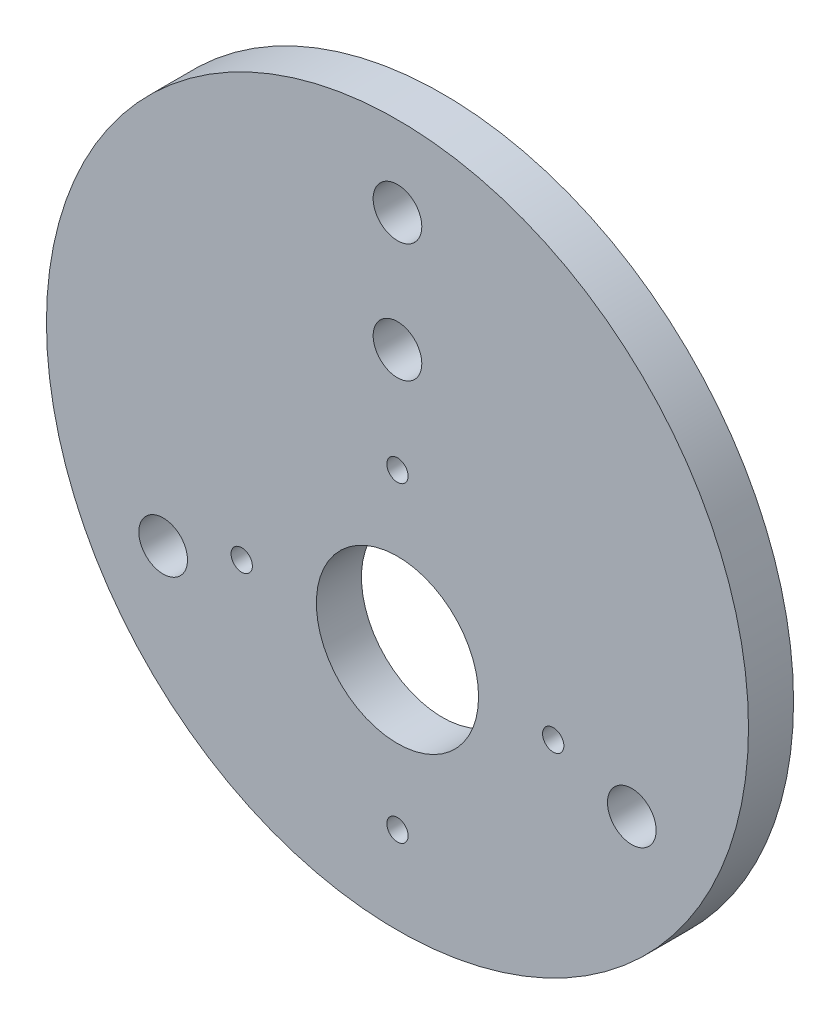
SolidWorks part; units mm, degrees
ref_plane "Front Plane" through (0, 0, 0) normal (0, 0, 1) x (1, 0, 0)
ref_plane "Top Plane" through (0, 0, 0) normal (0, 1, 0) x (1, 0, 0)
ref_plane "Right Plane" through (0, 0, 0) normal (1, 0, 0) x (0, 0, -1)
sketch "Sketch1" plane through (0, 0, 0) normal (0, 0, 1) x (1, 0, 0)
  circle A0 centre (0, 0) radius 49.4665
  dimension "D1" = 98.933
extrude "Boss-Extrude1" add sketch "Sketch1" along normal blind 6.35
sketch "Sketch2" plane through (0, 0, 6.35) normal (0, 0, 1) x (1, 0, 0)
  line L0 (0, -37.1877) -> (0, 6.7077) construction
  line L1 (-21.9477, -15.24) -> (0, 6.7077)
  line L2 (-21.9477, -15.24) -> (0, -37.1877)
  line L3 (0, -37.1877) -> (21.9477, -15.24)
  line L4 (0, 6.7077) -> (21.9477, -15.24)
  line L5 (0, -15.24) -> (12.0918, -15.24) construction
  point P4 (0, -15.24)
  dimension "D1" = 31.0388
  dimension "D2" = 31.0388
  dimension "D3" = 15.24
  dimension "D4" = 90
hole_wizard "M3 Screw Hole - Ø3.0mm Dowel Hole" positions "Sketch3" profile "Sketch4" hole size "Ø3.0" standard "ANSI Metric" end condition through all
sketch "Sketch3" plane through (0, 0, 6.35) normal (0, 0, 1) x (1, 0, 0)
  point P0 (0, 6.7077)
  point P3 (-21.9477, -15.24)
  point P6 (0, -37.1877)
  point P9 (21.9477, -15.24)
sketch "Sketch4" plane through (0, 6.7077, 6.35) normal (1, 0, 0) x (0, -1, 0)
  line L0 (0, 0) -> (0, 6.35)
  line L1 (0, 6.35) -> (1.5, 6.35)
  line L2 (1.5, 6.35) -> (1.5, 0)
  line L5 (1.5, 0) -> (0, 0)
  line L11 (0, -6.35) -> (0, 107.95) construction
  dimension "Thru Hole Dia." = 3
  dimension "Thru Hole Depth" = 6.35
sketch "Sketch5" plane through (0, 0, 6.35) normal (0, 0, 1) x (1, 0, 0)
  line L0 (0, -37.1877) -> (0, 6.7077) construction
  line L1 (-29.9941, -15.24) -> (0, 14.7541)
  line L2 (-29.9941, -15.24) -> (0, -45.2341)
  line L3 (0, -45.2341) -> (29.9941, -15.24)
  line L4 (0, 14.7541) -> (29.9941, -15.24)
  line L5 (-29.9941, -15.24) -> (29.9941, -15.24) construction
  line L6 (0, -45.2341) -> (0, 14.7541) construction
  line L7 (-19.3974, 4.1574) -> (0, -15.24) construction
  line L8 (0, -15.24) -> (19.3974, -15.24) construction
  line L9 (0, -15.24) -> (19.3974, -34.6374) construction
  line L10 (0, -15.24) -> (-3.0533, -18.2933) construction
  line L11 (-3.0533, -18.2933) -> (16.3441, -37.6906) construction
  line L12 (0, -15.24) -> (-19.3974, -34.6374) construction
  line L13 (0, -15.24) -> (-18.3197, 3.0797) construction
  line L14 (-18.3197, 3.0797) -> (0, 21.3994) construction
  circle A0 centre (0, 21.3994) radius 3.429
  circle A1 centre (16.3441, -37.6906) radius 3.429
  circle A2 centre (-19.3974, -34.6374) radius 3.429
  point P0 (0, -15.24)
  point P7 (0, -15.24)
  point P21 (19.3974, -15.24)
  dimension "D3" = 27.432
  dimension "D5" = 27.432
  dimension "D9" = 6.858
  dimension "D1" = 42.418
  dimension "D2" = 4.318
  dimension "D4" = 42.418
  dimension "D6" = 27.432
  dimension "D7" = 135
  dimension "D8" = 25.908
sketch "Sketch6" plane through (0, 0, 6.35) normal (0, 0, 1) x (1, 0, 0)
  line L0 (0, 38.1282) -> (-33.02, -19.0641) construction
  line L1 (-33.02, -19.0641) -> (33.02, -19.0641) construction
  line L2 (33.02, -19.0641) -> (0, 38.1282) construction
  line L3 (-33.02, -19.0641) -> (0, 0) construction
  line L4 (0, 0) -> (33.02, -19.0641) construction
  line L5 (0, 0) -> (0, 38.1282) construction
  circle A0 centre (0, 38.1282) radius 3.429
  circle A1 centre (-33.02, -19.0641) radius 3.429
  circle A2 centre (33.02, -19.0641) radius 3.429
  dimension "D1" = 6.858
  dimension "D2" = 66.04
  dimension "D3" = 60
  dimension "D4" = 60
extrude "Cut-Extrude2" cut sketch "Sketch6" against normal through all
sketch "Sketch7" plane through (0, 0, 6.35) normal (0, 0, 1) x (1, 0, 0)
  line L0 (0, -37.1877) -> (0, 6.7077) construction
  circle A0 centre (0, -15.24) radius 11.43
  point P4 (0, -15.24)
  dimension "D1" = 22.86
extrude "Cut-Extrude3" cut sketch "Sketch7" against normal through all
sketch "Possible Plate Hole Reference" plane through (0, 0, 6.35) normal (0, 0, 1) x (1, 0, 0)
  line L0 (47.781, 12.8029) -> (-47.781, -12.8029) construction
  line L1 (0, 0) -> (49.4665, 0) construction
  circle A0 centre (0, 0) radius 49.4665 construction
  circle A1 centre (0, 0) radius 4.9466 construction
  circle A2 centre (0, 0) radius 49.4665 construction
  point P7 (0, 0)
  dimension "D2" = 9.8933
  dimension "D3" = 98.933
  dimension "D1" = 15
extrude "Cut-Extrude4" cut sketch "Sketch5" against normal through all contours A0 region at (0, 21.3994, 6.35)
equation "\"D2@Possible Plate Hole Reference\" = 0.1 * \"D3@Possible Plate Hole Reference\""
